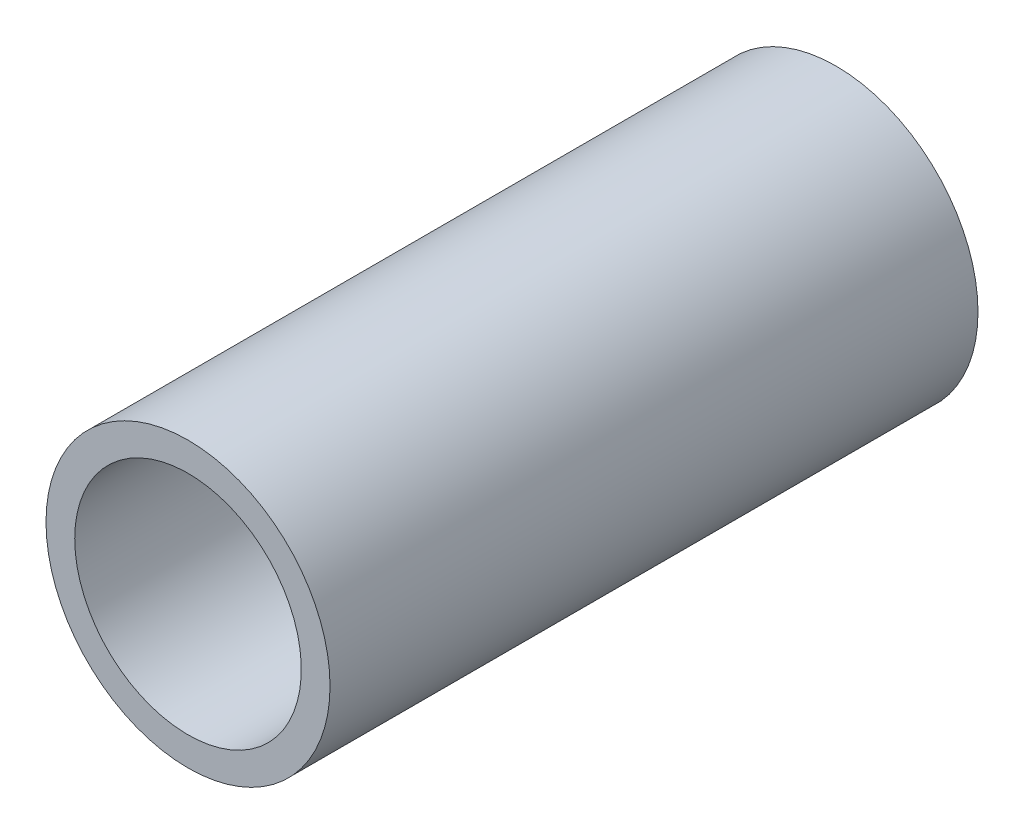
SolidWorks part; units mm, degrees
ref_plane "Front Plane" through (0, 0, 0) normal (0, 0, 1) x (1, 0, 0)
ref_plane "Top Plane" through (0, 0, 0) normal (0, 1, 0) x (1, 0, 0)
ref_plane "Right Plane" through (0, 0, 0) normal (1, 0, 0) x (0, 0, -1)
sketch "Sketch1" plane through (0, 0, 0) normal (0, 0, 1) x (1, 0, 0)
  circle A0 centre (0, 0) radius 16.7005
  dimension "Pipe OD" = 33.401
extrude "Extrude-Thin1" add sketch "Sketch1" along normal mid plane 76.2 thin thin type one direction reverse wall 3.3782
